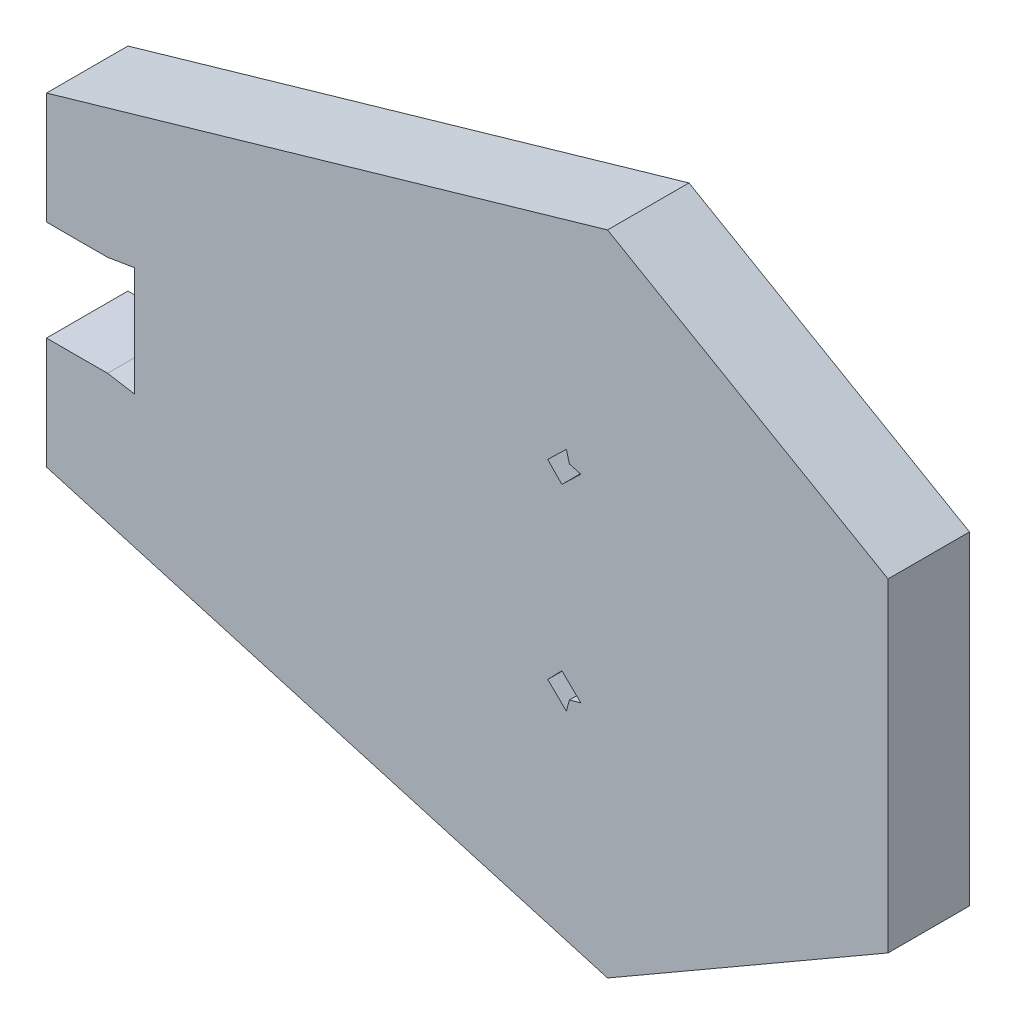
SolidWorks part; units mm, degrees
ref_plane "Front Plane" through (0, 0, 0) normal (0, 0, 1) x (1, 0, 0)
ref_plane "Top Plane" through (0, 0, 0) normal (0, 1, 0) x (1, 0, 0)
ref_plane "Right Plane" through (0, 0, 0) normal (1, 0, 0) x (0, 0, -1)
sketch "Sketch1" plane through (0, 0, 0) normal (0, 0, 1) x (1, 0, 0)
  line L0 (25.85, 11.9319) -> (5.1833, 23.8638) construction
  line L1 (25.85, -11.9319) -> (25.85, 11.9319) construction
  line L2 (5.1833, -23.8638) -> (25.85, -11.9319) construction
  line L3 (5.1833, -23.8638) -> (-36.15, -11.9319) construction
  line L4 (-36.15, 11.9319) -> (-36.15, -11.9319) construction
  line L5 (-36.15, 11.9319) -> (5.1833, 23.8638) construction
  line L6 (25.85, 11.9319) -> (5.1833, 23.8638)
  line L7 (25.85, -11.9319) -> (25.85, 11.9319)
  line L8 (5.1833, -23.8638) -> (25.85, -11.9319)
  line L9 (5.1833, -23.8638) -> (-36.15, -11.9319)
  line L10 (-36.15, 11.9319) -> (-36.15, -11.9319)
  line L11 (-36.15, 11.9319) -> (5.1833, 23.8638)
  line L18 (-36.15, 3.7) -> (-31.65, 3.7)
  line L19 (-31.65, 3.7) -> (-29.65, 4.0324)
  line L20 (-19.0706, 5.7908) -> (-31.65, 3.7) construction
  line L21 (-29.65, 4.0324) -> (-29.65, -4.0324)
  line L23 (-19.0706, -5.7908) -> (-31.65, -3.7) construction
  line L24 (-29.65, -4.0324) -> (-31.65, -3.7)
  line L25 (-31.65, -3.7) -> (-36.15, -3.7)
  line L26 (-34.65, 3.7) -> (-33.15, 3.7) construction
  line L27 (-31.65, 3.7) -> (-31.65, 1.5) construction
  line L28 (-36.15, 0) -> (25.85, 0) construction
  line L29 (2.151, -8.3523) -> (0.7764, -7.0196)
  line L30 (0.7764, -7.0196) -> (1.8203, -5.9429)
  line L31 (1.8203, -5.9429) -> (3.2171, -7.297)
  line L32 (3.2171, -7.297) -> (2.3753, -7.5253)
  line L33 (2.3753, 7.5253) -> (2.151, 8.3523)
  line L34 (2.3753, 7.5253) -> (2.151, 8.3523)
  line L35 (3.2171, 7.297) -> (2.3753, 7.5253)
  line L36 (3.2171, 7.297) -> (2.3753, 7.5253)
  line L37 (1.8203, 5.9429) -> (3.2171, 7.297)
  line L38 (1.8203, 5.9429) -> (3.2171, 7.297)
  line L39 (0.7764, 7.0196) -> (1.8203, 5.9429)
  line L40 (0.7764, 7.0196) -> (1.8203, 5.9429)
  line L41 (2.151, 8.3523) -> (0.7764, 7.0196)
  line L42 (2.151, 8.3523) -> (0.7764, 7.0196)
  line L43 (2.3753, -7.5253) -> (2.151, -8.3523)
  dimension "D1" = 2
  dimension "D2" = 0
extrude "Boss-Extrude1" add sketch "Sketch1" along normal blind 6 contours L28 L21 L24 L25 L10 L9 L8 L7 | L21 L28 L7 L6 L11 L10 L18 L19 region at (-3.3659, 9.4523, 0) region at (-3.3659, -9.4523, 0)
